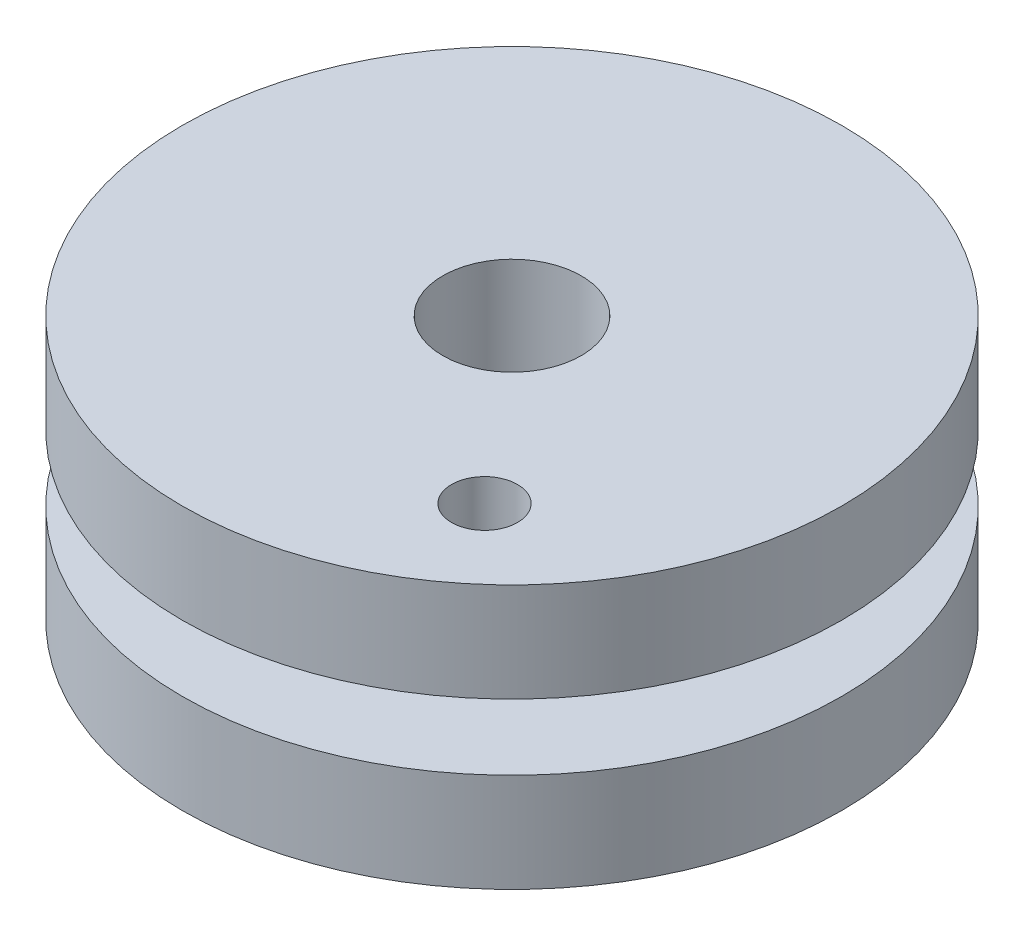
SolidWorks part; units mm, degrees
ref_plane "前视基准面" through (0, 0, 0) normal (0, 0, 1) x (1, 0, 0)
ref_plane "上视基准面" through (0, 0, 0) normal (0, 1, 0) x (1, 0, 0)
ref_plane "右视基准面" through (0, 0, 0) normal (1, 0, 0) x (0, 0, -1)
sketch "草图1" plane through (0, 0, 0) normal (0, 1, 0) x (1, 0, 0)
  circle A0 centre (0, 0) radius 10
  circle A1 centre (0, 0) radius 2.1
  dimension "D1" = 20
  dimension "D2" = 4.2
extrude "凸台-拉伸1" add sketch "草图1" along normal blind 8
sketch "草图2" plane through (0, 0, 0) normal (0, -1, 0) x (1, 0, 0)
  circle A0 centre (0, 0) radius 5
  circle A1 centre (0, 0) radius 10
  dimension "D1" = 10
extrude "切除-拉伸1" cut sketch "草图2" against normal blind 2 from offset 3 offset against normal yes
fillet "圆角1" radius 1 2 edges at (0, 5, -5) (0, 3, -5)
sketch "草图3" plane through (0, 8, 0) normal (0, 1, 0) x (1, 0, 0)
  circle A0 centre (4.5152, -5.3491) radius 1
  circle A1 centre (0, 0) radius 6 construction
  point P4 (4.5152, -5.3491)
  dimension "D1" = 2
extrude "切除-拉伸2" cut sketch "草图3" against normal up to next
